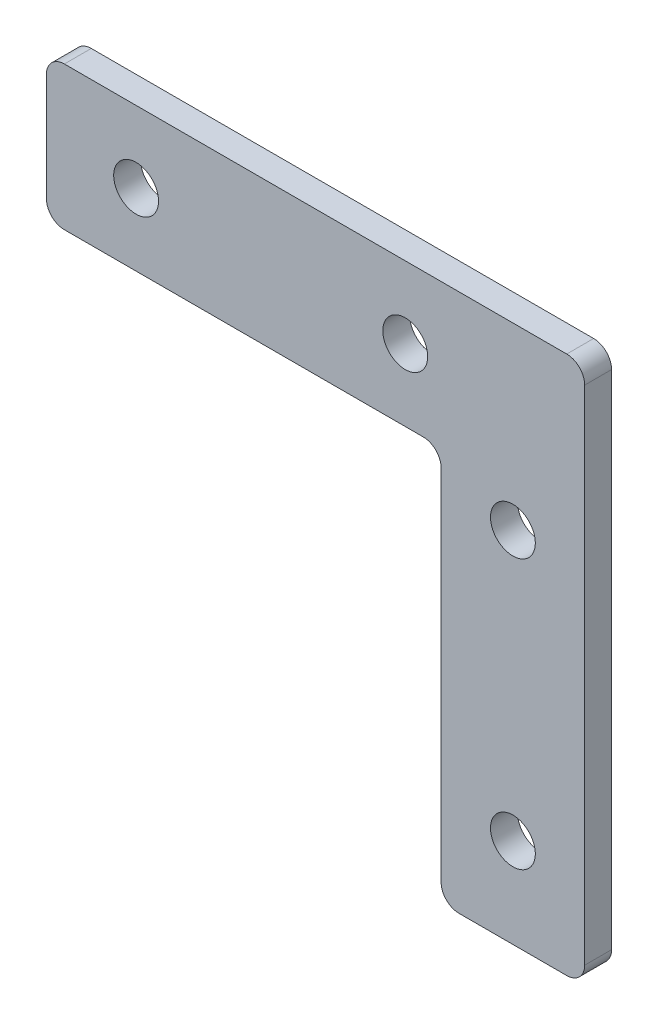
SolidWorks part; units mm, degrees
ref_plane "Płaszczyzna przednia" through (0, 0, 0) normal (0, 0, 1) x (1, 0, 0)
ref_plane "Płaszczyzna górna" through (0, 0, 0) normal (0, 1, 0) x (1, 0, 0)
ref_plane "Płaszczyzna prawa" through (0, 0, 0) normal (1, 0, 0) x (0, 0, -1)
sketch "Sketch1" plane through (0, 0, 0) normal (0, 0, 1) x (1, 0, 0)
  line L1 (0, 0) -> (44, 0)
  line L2 (0, 0) -> (0, 16)
  line L3 (0, 16) -> (60, 16)
  line L4 (60, 0) -> (60, 16)
  line L5 (0, 0) -> (60, 16) construction
  line L6 (0, 16) -> (60, 0) construction
  line L8 (60, 0) -> (60, -44)
  line L9 (60, -44) -> (44, -44)
  line L10 (44, 0) -> (44, -44)
  line L11 (60, 0) -> (44, -44) construction
  line L12 (60, -44) -> (44, 0) construction
  point P4 (30, 8)
  point P9 (52, -22)
  dimension "D1" = 60
  dimension "D2" = 16
  dimension "D3" = 44
  dimension "D4" = 16
extrude "Boss-Extrude1" add sketch "Sketch1" along normal blind 3
sketch "Sketch2" plane through (0, 0, 3) normal (0, 0, 1) x (1, 0, 0)
  line L0 (0, 0) -> (44, 0) construction
  line L1 (44, 0) -> (44, -44) construction
  line L2 (44, -44) -> (60, -44) construction
  line L3 (0, 16) -> (0, 0) construction
  line L4 (60, -44) -> (60, 16) construction
  line L5 (60, 16) -> (0, 16) construction
  circle A0 centre (10, 8) radius 2.5
  circle A1 centre (40, 8) radius 2.5
  circle A2 centre (52, -4) radius 2.5
  circle A3 centre (52, -34) radius 2.5
  dimension "D1" = 5
  dimension "D2" = 5
  dimension "D3" = 5
  dimension "D4" = 5
  dimension "D5" = 8
  dimension "D6" = 8
  dimension "D7" = 8
  dimension "D8" = 8
  dimension "D9" = 10
  dimension "D10" = 10
  dimension "D11" = 20
  dimension "D12" = 20
extrude "Cut-Extrude1" cut sketch "Sketch2" against normal blind 3
fillet "Fillet1" radius 2 6 edges at (44, -44, 1.5) (60, -44, 1.5) (44, 0, 1.5) (60, 16, 1.5) (0, 16, 1.5) (0, 0, 1.5)
